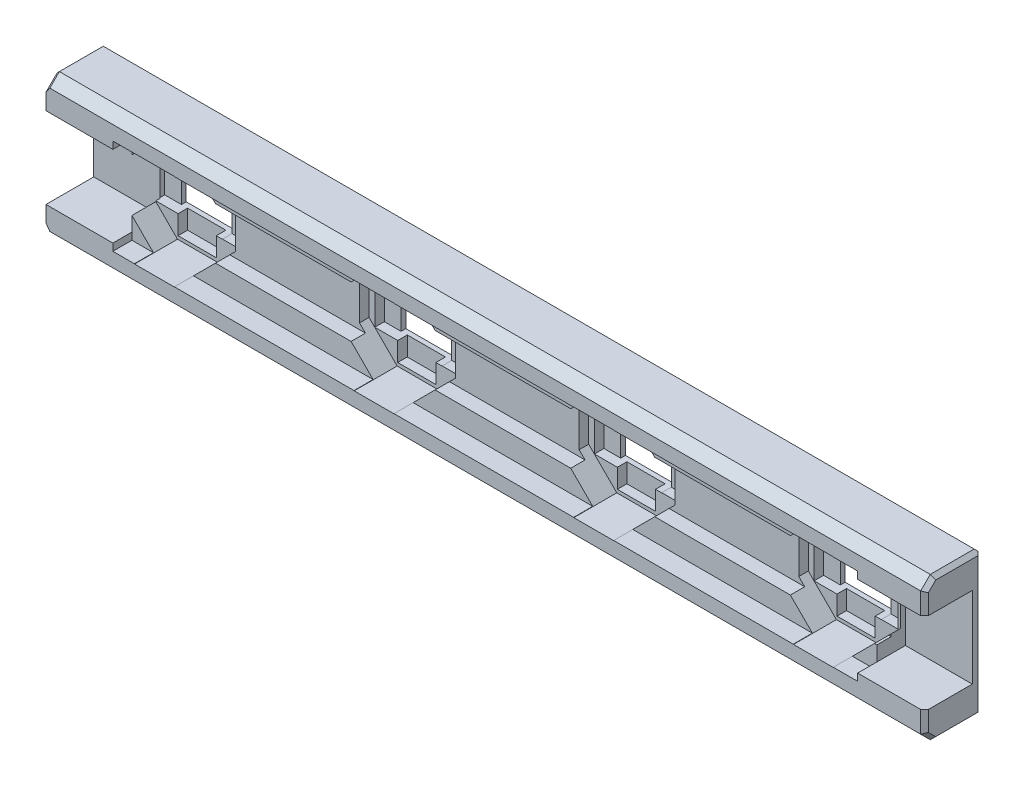
SolidWorks part; units mm, degrees
ref_plane "Front Plane" through (0, 0, 0) normal (0, 0, 1) x (1, 0, 0)
ref_plane "Top Plane" through (0, 0, 0) normal (0, 1, 0) x (1, 0, 0)
ref_plane "Right Plane" through (0, 0, 0) normal (1, 0, 0) x (0, 0, -1)
sketch "Sketch1" plane through (0, 0, 0) normal (0, 0, 1) x (1, 0, 0)
  line L1 (-45.75, 25.6543) -> (46.25, 25.6543)
  line L2 (-45.75, 25.6543) -> (-45.75, 10.6543)
  line L3 (-45.75, 10.6543) -> (46.25, 10.6543)
  line L4 (46.25, 25.6543) -> (46.25, 10.6543)
  dimension "D1" = 92
  dimension "D2" = 15
extrude "Boss-Extrude1" add sketch "Sketch1" along normal blind 6
sketch "Sketch12" plane through (46.25, 0, 0) normal (1, 0, 0) x (0, 0, -1)
  line L0 (-6, 25.6543) -> (-6, 24.6543)
  line L1 (-6, 10.6543) -> (-6, 25.6543) construction
  line L2 (-6, 24.6543) -> (-5, 25.6543)
  line L3 (-6, 25.6543) -> (0, 25.6543) construction
  line L4 (-5, 25.6543) -> (-6, 25.6543)
  line L5 (-6, 10.6543) -> (-5, 10.6543)
  line L6 (-6, 10.6543) -> (0, 10.6543) construction
  line L7 (-5, 10.6543) -> (-6, 11.6543)
  line L8 (-6, 10.6543) -> (-6, 25.6543) construction
  line L9 (-6, 11.6543) -> (-6, 10.6543)
  dimension "D1" = 1
  dimension "D2" = 1
  dimension "D3" = 1
extrude "Cut-Extrude8" cut sketch "Sketch12" against normal blind 92
sketch "Sketch13" plane through (0, 0, 0) normal (0, 0, -1) x (-1, 0, 0)
  line L0 (45.75, 25.6543) -> (45.75, 10.6543) construction
  line L1 (43.25, 23.1543) -> (43.75, 23.1543)
  line L2 (43.25, 23.1543) -> (43.25, 13.1543)
  line L3 (43.25, 13.1543) -> (43.75, 13.1543)
  line L4 (43.75, 23.1543) -> (43.75, 13.1543)
  line L5 (-46.25, 25.6543) -> (45.75, 25.6543) construction
  dimension "D1" = 2
  dimension "D2" = 0.5
  dimension "D3" = 10
  dimension "D4" = 2.5
extrude "Cut-Extrude9" cut sketch "Sketch13" against normal blind 0.6
fillet "Fillet1" radius 0.25 1 edges at (-43.75, 18.1543, 0)
fillet "Fillet2" radius 0.25 4 edges at (-43.5, 23.1543, 0.6) (-43.75, 18.1543, 0.6) (-43.5, 13.1543, 0.6) (-43.25, 18.1543, 0.6)
chamfer "Chamfer1" distance 0.4 angle 45 2 edges at (0.25, 10.6543, 0) (0.25, 25.6543, 0)
chamfer "Chamfer2" distance 0.4 angle 45 2 edges at (46.25, 18.1543, 0) (-45.75, 18.1543, 0)
chamfer "Chamfer3" distance 0.4 angle 45 2 edges at (-45.75, 10.6543, 2.7) (-45.75, 25.6543, 2.7)
chamfer "Chamfer4" distance 0.4 angle 45 2 edges at (-45.75, 11.3543, 5.7) (-45.75, 24.9543, 5.7)
chamfer "Chamfer5" distance 0.4 angle 45 5 edges at (46.25, 25.1543, 5.5) (46.25, 25.6543, 2.7) (46.25, 18.1543, 6) (46.25, 11.1543, 5.5) (46.25, 10.6543, 2.7)
sketch "Sketch15" plane through (0, 0, 6) normal (0, 0, 1) x (1, 0, 0)
  line L0 (-45.75, 24.0886) -> (-45.75, 12.22) construction
  line L1 (-29.3821, 20.2328) -> (-32.3215, 23.1722)
  line L2 (-32.3215, 23.1722) -> (-36.4785, 23.1722)
  line L3 (-36.4785, 23.1722) -> (-39.4179, 20.2328)
  line L4 (-39.4179, 20.2328) -> (-39.4179, 16.0758)
  line L5 (-39.4179, 16.0758) -> (-36.4785, 13.1364)
  line L6 (-36.4785, 13.1364) -> (-32.3215, 13.1364)
  line L7 (-32.3215, 13.1364) -> (-29.3821, 16.0758)
  line L8 (-29.3821, 16.0758) -> (-29.3821, 20.2328)
  line L9 (-45.35, 25.6543) -> (45.85, 25.6543) construction
  line L10 (-45.35, 11.6543) -> (45.85, 11.6543) construction
  circle A0 centre (-34.4, 18.1543) radius 5.0179 construction
  dimension "D1" = 11.35
  dimension "D2" = 7.5
extrude "Cut-Extrude10" cut sketch "Sketch15" against normal blind 4.5
sketch "Sketch16" plane through (0, 0, 1.5) normal (0, 0, 1) x (1, 0, 0)
  line L1 (-37.0679, 20.7864) -> (-31.7679, 20.7864)
  line L2 (-37.0679, 20.7864) -> (-37.0679, 15.4864)
  line L3 (-37.0679, 15.4864) -> (-31.7679, 15.4864)
  line L4 (-31.7679, 20.7864) -> (-31.7679, 15.4864)
  line L5 (-39.4179, 20.2328) -> (-39.4179, 16.0758) construction
  line L6 (-36.4785, 13.1364) -> (-32.3215, 13.1364) construction
  point P4 (-37.0679, 18.1364)
  point P7 (-39.4179, 18.1543)
  point P10 (-34.4, 13.1364)
  point P11 (-34.4179, 15.4864)
  dimension "D1" = 5.3
  dimension "D2" = 5.3
  dimension "D3" = 2.35
  dimension "D4" = 2.35
extrude "Cut-Extrude11" cut sketch "Sketch16" against normal blind 4.5
sketch "Sketch17" plane through (0, 0, 1.5) normal (0, 0, 1) x (1, 0, 0)
  line L0 (-37.0679, 15.4864) -> (-31.7679, 15.4864) construction
  line L1 (-36.4179, 15.4864) -> (-32.4179, 15.4864)
  line L2 (-36.4179, 15.4864) -> (-36.4179, 13.4864)
  line L3 (-36.4179, 13.4864) -> (-32.4179, 13.4864)
  line L4 (-32.4179, 15.4864) -> (-32.4179, 13.4864)
  line L5 (-31.7679, 20.7864) -> (-37.0679, 20.7864) construction
  line L6 (-36.4179, 20.7864) -> (-32.4179, 20.7864)
  line L7 (-36.4179, 20.7864) -> (-36.4179, 22.7864)
  line L8 (-36.4179, 22.7864) -> (-32.4179, 22.7864)
  line L9 (-32.4179, 20.7864) -> (-32.4179, 22.7864)
  line L10 (-31.7679, 15.4864) -> (-31.7679, 20.7864) construction
  dimension "D1" = 4
  dimension "D2" = 4
  dimension "D3" = 2
  dimension "D4" = 2
  dimension "D5" = 0.65
  dimension "D6" = 0.65
extrude "Cut-Extrude12" cut sketch "Sketch17" against normal blind 1
sketch "Sketch18" plane through (0, 0, 1.5) normal (0, 0, 1) x (1, 0, 0)
  line L1 (-37.0679, 15.4864) -> (-38.8179, 15.4864)
  line L2 (-37.0679, 15.4864) -> (-37.0679, 20.8045)
  line L3 (-37.0679, 20.8045) -> (-38.8179, 20.8045)
  line L4 (-38.8179, 15.4864) -> (-38.8179, 20.8045)
  line L5 (-31.7679, 20.7864) -> (-30.0179, 20.7864)
  line L6 (-31.7679, 20.7864) -> (-31.7679, 15.5045)
  line L7 (-31.7679, 15.5045) -> (-30.0179, 15.5045)
  line L8 (-30.0179, 20.7864) -> (-30.0179, 15.5045)
  dimension "D1" = 1.75
  dimension "D2" = 1.75
extrude "Cut-Extrude13" cut sketch "Sketch18" against normal blind 1
pattern_linear "LPattern1" count 4 spacing 23 along (1, 0, 0) of "Cut-Extrude10", "Cut-Extrude11", "Cut-Extrude12", "Cut-Extrude13"
sketch "Sketch19" plane through (0, 0, 6) normal (0, 0, 1) x (1, 0, 0)
  line L0 (-45.75, 24.0886) -> (-45.75, 12.22) construction
  line L1 (-45.75, 22.4043) -> (-38.75, 22.4043)
  line L2 (-45.75, 22.4043) -> (-45.75, 13.9043)
  line L3 (-45.75, 13.9043) -> (-38.75, 13.9043)
  line L4 (-38.75, 22.4043) -> (-38.75, 13.9043)
  line L6 (-45.35, 10.6543) -> (45.85, 10.6543) construction
  line L14 (46.25, 24.4886) -> (46.25, 11.82) construction
  line L15 (46.25, 22.4043) -> (39.25, 22.4043)
  line L16 (46.25, 22.4043) -> (46.25, 13.9043)
  line L17 (46.25, 13.9043) -> (39.25, 13.9043)
  line L18 (39.25, 22.4043) -> (39.25, 13.9043)
  dimension "D1" = 8.5
  dimension "D2" = 3.25
  dimension "D3" = 7
  dimension "D4" = 8.5
  dimension "D5" = 7
  dimension "D6" = 3.25
extrude "Cut-Extrude14" cut sketch "Sketch19" against normal blind 5
sketch "Sketch20" plane through (0, 0, 6) normal (0, 0, 1) x (1, 0, 0)
  line L0 (-45.35, 10.6543) -> (45.85, 10.6543) construction
  line L1 (39.25, 13.1543) -> (-38.75, 13.1543)
  line L2 (39.25, 13.1543) -> (39.25, 23.1543)
  line L3 (39.25, 23.1543) -> (-38.75, 23.1543)
  line L4 (-38.75, 13.1543) -> (-38.75, 23.1543)
  line L6 (-38.75, 20.9007) -> (-38.75, 22.4043) construction
  dimension "D1" = 10
  dimension "D2" = 2.5
  dimension "D3" = 0
extrude "Cut-Extrude15" cut sketch "Sketch20" against normal blind 2
sketch "Sketch21" plane through (29.5821, 0, 0) normal (1, 0, 0) x (0, 0, -1)
  line L0 (-4, 20.6007) -> (-4, 22.4043) construction
  line L3 (-4, 20.8507) -> (-2.5, 20.8507)
  line L4 (-4, 20.8507) -> (-4, 15.4579)
  line L5 (-4, 15.4579) -> (-2.5, 15.4579)
  line L6 (-2.5, 20.8507) -> (-2.5, 15.4579)
  line L7 (-1.5, 20.6007) -> (-4, 20.6007) construction
  line L8 (-4, 15.7079) -> (-1.5, 15.7079) construction
  dimension "D2" = 0.25
  dimension "D3" = 0.25
  dimension "D1" = 1.5
extrude "Cut-Extrude16" cut sketch "Sketch21" against normal through all both and the other way through all
